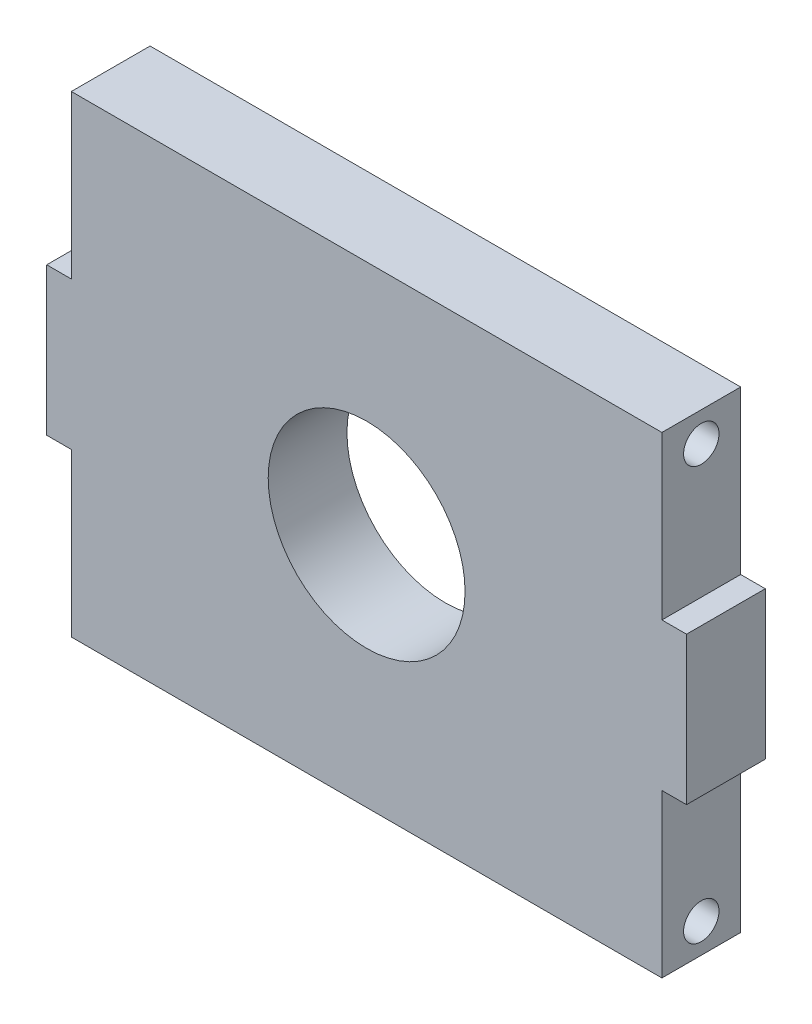
SolidWorks part; units mm, degrees
material "3d打印 35%"
ref_plane "前视基准面" through (0, 0, 0) normal (0, 0, 1) x (1, 0, 0)
ref_plane "上视基准面" through (0, 0, 0) normal (0, 1, 0) x (1, 0, 0)
ref_plane "右视基准面" through (0, 0, 0) normal (1, 0, 0) x (0, 0, -1)
sketch "草图1" plane through (0, 0, 0) normal (0, 0, 1) x (1, 0, 0)
  line L1 (30, 24) -> (-30, 24)
  line L2 (30, 24) -> (30, -24)
  line L3 (30, -24) -> (-30, -24)
  line L4 (-30, 24) -> (-30, -24)
  line L5 (30, 24) -> (-30, -24) construction
  line L6 (30, -24) -> (-30, 24) construction
  point P0 (0, 0)
  dimension "D1" = 60
  dimension "D2" = 48
extrude "凸台-拉伸1" add sketch "草图1" along normal blind 8 contours L1 L4 L3 L2
ref_plane "基准面4" through (30, -24, 8) normal (-1, 0, 0) x (0, 0, 1)
sketch "草图3" plane through (0, 0, 8) normal (0, 0, 1) x (1, 0, 0)
  line L1 (-32.5, 7.5) -> (32.5, 7.5)
  line L2 (-32.5, 7.5) -> (-32.5, -7.5)
  line L3 (-32.5, -7.5) -> (32.5, -7.5)
  line L4 (32.5, 7.5) -> (32.5, -7.5)
  line L5 (-32.5, 7.5) -> (32.5, -7.5) construction
  line L6 (-32.5, -7.5) -> (32.5, 7.5) construction
  point P1 (0, 0)
  dimension "D1" = 15
  dimension "D2" = 65
extrude "凸台-拉伸2" add sketch "草图3" against normal blind 8
ref_plane "基准面5" through (0, 0, 4) normal (0, 0, -1) x (-1, 0, 0)
ref_axis "基准轴1" through (30, 26.4, 4) along (0, -1, 0)
sketch "草图5" plane through (30, 0, 0) normal (1, 0, 0) x (0, 0, -1)
  line L0 (-4, -26.4) -> (-4, 26.4) construction
  line L1 (-8, 24) -> (0, 24) construction
  circle A0 centre (-4, 21) radius 1.8
  dimension "D1" = 3
extrude "切除-拉伸1" cut sketch "草图5" against normal blind 3
ref_plane "基准面6" through (0, 0, 0) normal (1, 0, 0) x (0, 0, -1)
ref_plane "基准面7" through (0, 0, 0) normal (0, 1, 0) x (1, 0, 0)
mirror "镜向2" about plane through (0, 0, 0) normal (0, 1, 0) of "切除-拉伸1"
mirror "镜向3" about plane through (0, 0, 0) normal (1, 0, 0) of "镜向2"
sketch "草图7" plane through (0, 0, 8) normal (0, 0, 1) x (1, 0, 0)
  circle A0 centre (0, 0) radius 10
extrude "切除-拉伸2" cut sketch "草图7" against normal blind 8
